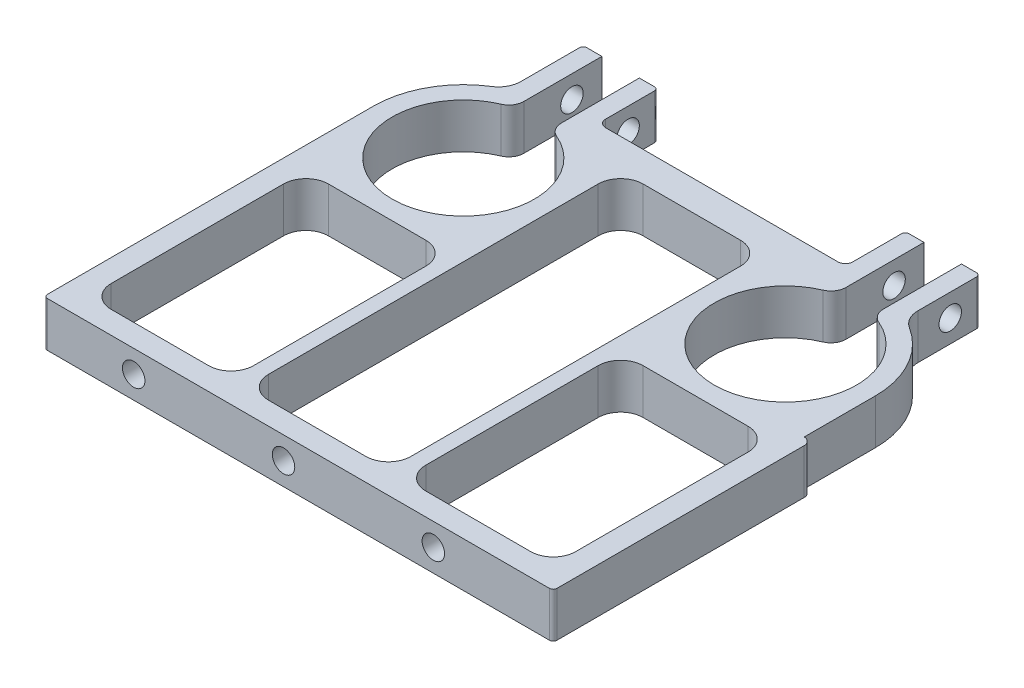
SolidWorks part; units mm, degrees
ref_plane "前视基准面" through (0, 0, 0) normal (0, 0, 1) x (1, 0, 0)
ref_plane "上视基准面" through (0, 0, 0) normal (0, 1, 0) x (1, 0, 0)
ref_plane "右视基准面" through (0, 0, 0) normal (1, 0, 0) x (0, 0, -1)
sketch "草图1" plane through (0, 0, 0) normal (0, 1, 0) x (1, 0, 0)
  line L0 (22, -25) -> (22, -54)
  line L1 (17, 0) -> (50, 0)
  line L2 (0, -13) -> (0, -57)
  line L3 (0, -57) -> (68, -57)
  line L4 (68, -22.5) -> (68, -57)
  line L5 (24, -25) -> (24, -54)
  line L6 (43, -25) -> (43, -54)
  line L7 (45, -25) -> (45, -54)
  line L8 (24, -25) -> (24, -4)
  line L9 (3, -25) -> (22, -25)
  line L10 (3, -25) -> (3, -54)
  line L11 (3, -54) -> (22, -54)
  line L12 (65, -25) -> (65, -54)
  line L13 (24, -4) -> (43, -4)
  line L14 (43, -4) -> (43, -25)
  line L15 (24, -54) -> (43, -54)
  line L16 (45, -25) -> (65, -25)
  line L17 (45, -54) -> (65, -54)
  line L18 (12, -13) -> (55, -13) construction
  line L19 (12, -13) -> (12, 4.4967) construction
  line L20 (7, -2.0913) -> (7, 8)
  line L21 (17, 0) -> (17, 8)
  line L22 (9.5, -3.8348) -> (9.5, 8)
  line L23 (14.5, 8) -> (17, 8)
  line L24 (14.5, -3.8348) -> (14.5, 8)
  line L25 (33.5, -12) -> (33.5, 8) construction
  line L26 (50, 0) -> (50, 8)
  line L27 (7, 8) -> (9.5, 8)
  line L28 (52.5, 8) -> (50, 8)
  line L29 (52.5, -3.8348) -> (52.5, 8)
  line L30 (57.5, -3.8348) -> (57.5, 8)
  line L31 (60, 8) -> (57.5, 8)
  line L32 (60, -2.0913) -> (60, 8)
  line L33 (67, -13) -> (67, -22.5)
  line L34 (67, -22.5) -> (68, -22.5)
  arc A0 (9.5, -3.8348) -> (14.5, -3.8348) centre (12, -13) ccw
  arc A1 (52.5, -3.8348) -> (57.5, -3.8348) centre (55, -13) ccw
  arc A2 (60, -2.0913) -> (67, -13) centre (55, -13) cw
  arc A4 (7, -2.0913) -> (0, -13) centre (12, -13) ccw
  point P11 (0, 0)
  dimension "D4" = 19
  dimension "D7" = 5
  dimension "D1" = 57
  dimension "D2" = 68
  dimension "D5" = 43
  dimension "D6" = 12
  dimension "D9" = 44
  dimension "D10" = 44
  dimension "D11" = 3
  dimension "D12" = 3
  dimension "D13" = 3
  dimension "D14" = 29
  dimension "D15" = 12
  dimension "D16" = 2
  dimension "D17" = 12
  dimension "D18" = 2
  dimension "D19" = 4
  dimension "D20" = 10
  dimension "D21" = 9.5
  dimension "D22" = 8
  dimension "D23" = 1
extrude "凸台-拉伸1" add sketch "草图1" along normal blind 6
sketch "草图3" plane through (0, 0, 57) normal (0, 0, 1) x (1, 0, 0)
  line L0 (0, 3) -> (81.2777, 3) construction
  line L1 (0, 6) -> (0, 0) construction
  circle A0 centre (12, 3) radius 1.5
  circle A1 centre (32, 3) radius 1.5
  circle A2 centre (52, 3) radius 1.5
  dimension "D1" = 3
  dimension "D2" = 3
  dimension "D3" = 3
  dimension "D4" = 12
  dimension "D5" = 20
  dimension "D6" = 20
extrude "切除-拉伸1" cut sketch "草图3" against normal blind 10
fillet "圆角1" radius 3 12 edges at (45, 3, 54) (24, 3, 54) (45, 3, 25) (24, 3, 4) (43, 3, 4) (65, 3, 25) (22, 3, 25) (65, 3, 54) (43, 3, 54) (22, 3, 54) (3, 3, 25) (3, 3, 54)
fillet "圆角2" radius 1 3 edges at (50, 3, 0) (17, 3, 0) (68, 3, 22.5)
sketch "草图4" plane through (7, 0, 0) normal (-1, 0, 0) x (0, 0, 1)
  line L0 (-8, 6) -> (2.0913, 6) construction
  line L1 (-8, 6) -> (-8, 0) construction
  circle A0 centre (-4, 3) radius 1.5
  dimension "D1" = 3
  dimension "D2" = 3
  dimension "D3" = 4
extrude "切除-拉伸2" cut sketch "草图4" against normal blind 72
fillet "圆角3" radius 0.5 2 edges at (68, 3, 57) (0, 3, 57)
fillet "圆角4" radius 0.5 4 edges at (60, 3, -8) (50, 3, -8) (17, 3, -8) (7, 3, -8)
fillet "圆角5" radius 3 2 edges at (7, 3, 2.0913) (60, 3, 2.0913)
fillet "圆角6" radius 2 4 edges at (52.5, 3, 3.8348) (57.5, 3, 3.8348) (14.5, 3, 3.8348) (9.5, 3, 3.8348)
